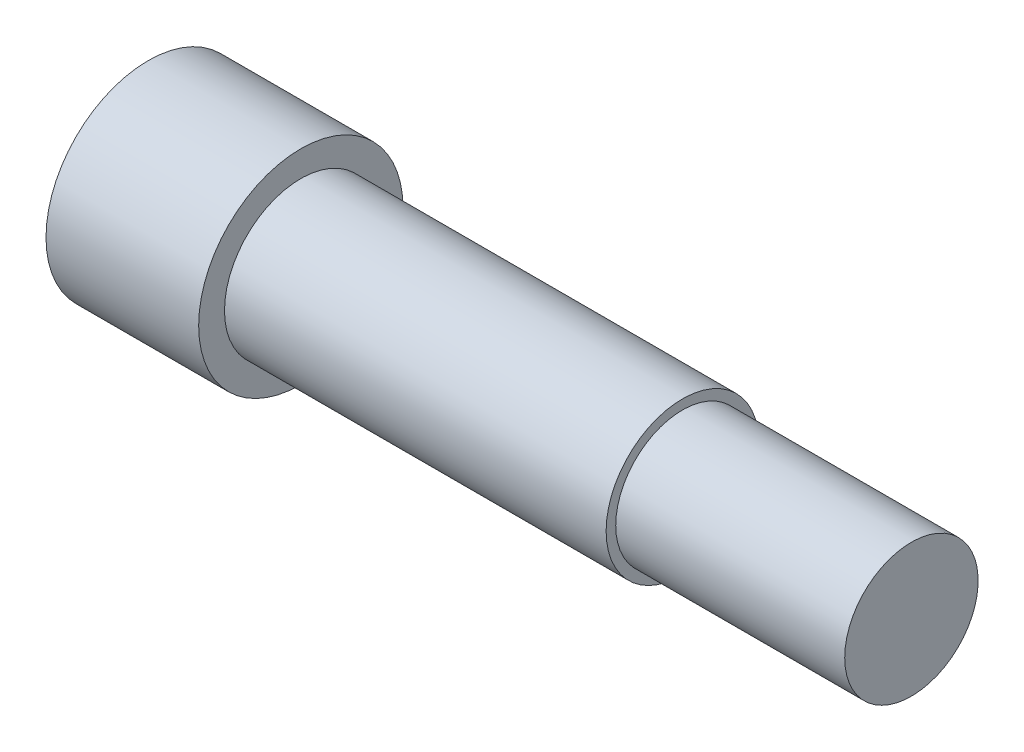
SolidWorks part; units mm, degrees
ref_plane "Front Plane" through (0, 0, 0) normal (0, 0, 1) x (1, 0, 0)
ref_plane "Top Plane" through (0, 0, 0) normal (0, 1, 0) x (1, 0, 0)
ref_plane "Right Plane" through (0, 0, 0) normal (1, 0, 0) x (0, 0, -1)
sketch "Sketch1" plane through (0, 0, 0) normal (0, 0, 1) x (1, 0, 0)
  line L0 (0, 0) -> (63.5, 0)
  line L1 (63.5, 0) -> (63.5, 5.5499)
  line L2 (63.5, 5.5499) -> (44.45, 5.5499)
  line L3 (12.7, 6.35) -> (12.7, 8.5)
  line L4 (12.7, 8.5) -> (0, 8.5)
  line L5 (0, 8.5) -> (0, 0)
  line L6 (12.7, 6.35) -> (44.45, 6.35)
  line L7 (44.45, 6.35) -> (44.45, 5.5499)
  dimension "D2" = 5.5499
  dimension "D4" = 12.7
  dimension "D3" = 8.5
  dimension "D1" = 31.75
  dimension "D5" = 19.05
  dimension "D6" = 6.35
revolve "Revolve1" add sketch "Sketch1" angle 360 about L0
cosmetic thread "Cosmetic Thread1" parameters "D2"=9.6012
equation "\"len\"=1.25"
equation "\"D1@Sketch1\"=\"len\""
equation "\"Cavity_Depth\" = 0.031in"
equation "\"Cavity_Width\" = 0.031in"
equation "\"Tooth_Width\" = .01in"
equation "\"Shaft_Seal_OD\"= 17mm'diameter at seal area"
equation "\"Shaft_clearance\"= .002in"
equation "\"O-Ring_ID\"= .801in"
equation "\"O-Ring_CS\"= .070in"
equation "\"Shaft_OD\"= .5in"
equation "\"D3@Sketch1\"=\"Shaft_Seal_OD\"/2"
equation "\"D6@Sketch1\"=\"Shaft_OD\"/2"
